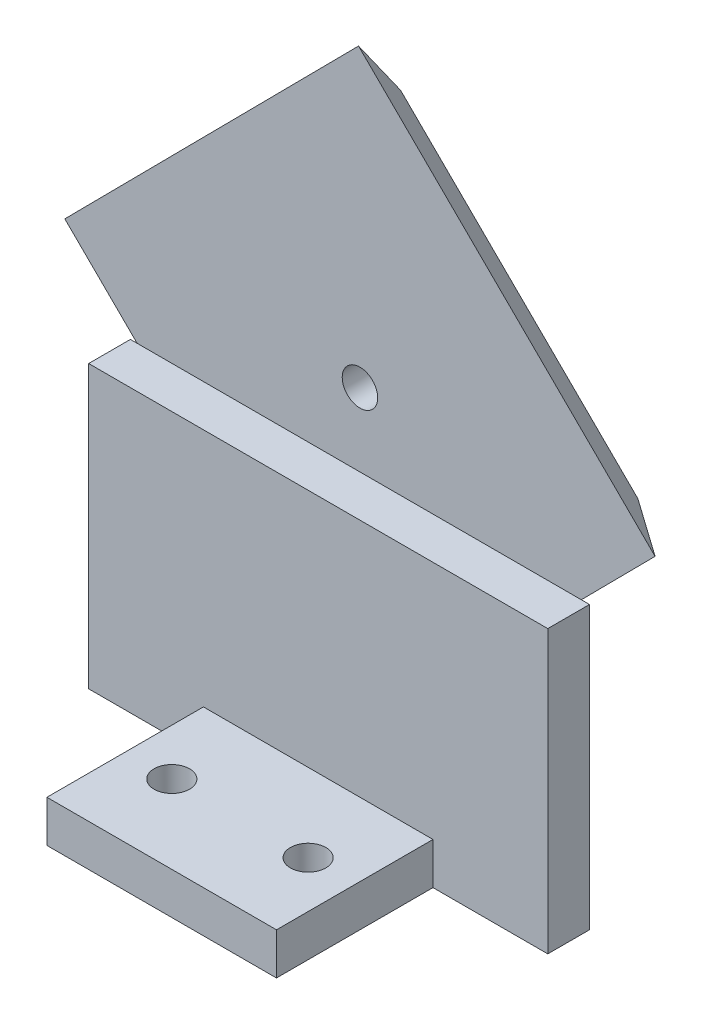
SolidWorks part; units mm, degrees
ref_plane "Спереди" through (0, 0, 0) normal (0, 0, 1) x (1, 0, 0)
ref_plane "Сверху" through (0, 0, 0) normal (0, 1, 0) x (1, 0, 0)
ref_plane "Справа" through (0, 0, 0) normal (1, 0, 0) x (0, 0, -1)
sketch "Эскиз1" plane through (0, 0, 0) normal (0, 1, 0) x (1, 0, 0)
  line L0 (-11, 7.5) -> (-11, 11.5)
  line L1 (11, 7.5) -> (-11, 7.5)
  line L2 (11, 7.5) -> (11, -7.5)
  line L3 (11, -7.5) -> (-11, -7.5)
  line L4 (-11, 7.5) -> (-11, -7.5)
  line L5 (11, 7.5) -> (-11, -7.5) construction
  line L6 (11, -7.5) -> (-11, 7.5) construction
  line L7 (-11, 11.5) -> (11, 11.5)
  line L8 (11, 11.5) -> (11, 7.5)
  line L9 (0, 7.5) -> (0, 11.5) construction
  line L10 (11, 11.5) -> (11, 21.5)
  line L11 (-22, 11.5) -> (22, 11.5)
  line L12 (-22, 11.5) -> (-22, 7.5)
  line L13 (-22, 7.5) -> (22, 7.5)
  line L14 (22, 11.5) -> (22, 7.5)
  line L15 (-22, 11.5) -> (22, 7.5) construction
  line L16 (-22, 7.5) -> (22, 11.5) construction
  line L17 (11, 21.5) -> (-11, 21.5)
  line L18 (-11, 21.5) -> (-11, 11.5)
  point P0 (0, 0)
  point P10 (0, 9.5)
  dimension "D1" = 22
  dimension "D2" = 15
  dimension "D3" = 4
  dimension "D4" = 44
  dimension "D5" = 10
extrude "Бобышка-Вытянуть1" add sketch "Эскиз1" along normal blind 4 contours L1 L4 L3 L2 region at (0, 0, 0)
sketch "Эскиз2" plane through (0, 0, 0) normal (0, -1, 0) x (1, 0, 0)
  line L0 (6.5317, 0) -> (-6.5317, 0)
  point P4 (0, 0)
  point P6 (6.5317, 0)
  point P7 (-6.5317, 0)
hole_wizard "Зенковка для винта с потайной головкой M31" positions "Трехмерный эскиз1" profile "Эскиз3" countersink size "M3" standard "DIN" end condition up to next
sketch3d "Трехмерный эскиз1"
  point P0 (6.5317, 0, 0)
  point P3 (-6.5317, 0, 0)
sketch "Эскиз3" plane through (6.5317, 0, 0) normal (1, 0, 0) x (0, 0, -1)
  line L0 (0, 0) -> (0, 4)
  line L1 (0, 4) -> (1.7, 4)
  line L2 (1.7, 4) -> (1.7, 1.45)
  line L3 (1.7, 1.45) -> (3.15, 0)
  line L5 (3.15, 0) -> (0, 0)
  line L6 (-1.7, 1.45) -> (-3.15, 0) construction
  line L11 (0, -6.35) -> (0, 107.95) construction
  dimension "Диаметр сквозного отверстия" = 3.4
  dimension "Глубина сквозного отверстия" = 4
  dimension "Диаметр передней зенковки" = 6.3
  dimension "Угол передней зенковки" = 90
extrude "Бобышка-Вытянуть2" add sketch "Эскиз1<5>" along normal blind 27 contours L14 L11 L8 L13 | L8 L7 L0 L1 | L12 L13 L0 L11 region at (-16.5, 0, -9.5) region at (0, 0, -9.5) region at (16.5, 0, -9.5)
sketch "Эскиз1<5>" plane through (0, 0, 0) normal (0, 1, 0) x (1, 0, 0) same geometry as "Эскиз1"
sketch "Эскиз4" plane through (0, 0, -11.5) normal (0, 0, -1) x (-1, 0, 0)
  line L0 (0, 0) -> (0, 34) construction
  line L1 (22, 0) -> (-22, 0) construction
  line L2 (0.1363, 62.2839) -> (28.2839, 33.8637)
  line L3 (0.1363, 62.2839) -> (-28.2839, 34.1363)
  line L4 (28.2839, 33.8637) -> (-0.1363, 5.7161)
  line L5 (-28.2839, 34.1363) -> (-0.1363, 5.7161)
  line L6 (0.1363, 62.2839) -> (-0.1363, 5.7161) construction
  line L7 (28.2839, 33.8637) -> (-28.2839, 34.1363) construction
  dimension "D1" = 34
  dimension "D2" = 40
extrude "Бобышка-Вытянуть3" add sketch "Эскиз4" along normal blind 4
draft "Уклон2" type of draft neutral plane draft angle 45 faces to draft 4 face at (15.6113, 21.3409, -13.1) face at (14.0738, 48.2101, -13.5) face at (-14.2101, 48.0738, -13.5) face at (-15.5298, 21.2319, -13.1) neutral plane through (0, 27, -11.5) neutral plane normal (0, 0, -1) parameters "D1"=45
sketch "Эскиз6" plane through (0, 0, -15.5) normal (0, 0, -1) x (-1, 0, 0)
  line L0 (-22.6272, 34.1091) -> (22.6272, 33.8909) construction
  point P4 (0, 34)
hole_wizard "Зенковка для винта с потайной головкой M32" positions "Трехмерный эскиз2" profile "Эскиз7" countersink size "M3" standard "DIN" end condition up to next
sketch3d "Трехмерный эскиз2"
  point P0 (0, 34, -15.5)
sketch "Эскиз7" plane through (0, 34, -15.5) normal (1, 0, 0) x (0, 1, 0)
  line L0 (0, 0) -> (0, 4)
  line L1 (0, 4) -> (1.7, 4)
  line L2 (1.7, 4) -> (1.7, 1.45)
  line L3 (1.7, 1.45) -> (3.15, 0)
  line L5 (3.15, 0) -> (0, 0)
  line L6 (-1.7, 1.45) -> (-3.15, 0) construction
  line L11 (0, -6.35) -> (0, 107.95) construction
  dimension "Диаметр сквозного отверстия" = 3.4
  dimension "Глубина сквозного отверстия" = 4
  dimension "Диаметр передней зенковки" = 6.3
  dimension "Угол передней зенковки" = 90
extrude "Бобышка-Вытянуть4" add sketch "Эскиз1<6>" along normal blind 4 contours L17 L18 L7 L10 region at (0, 0, -16.5)
sketch "Эскиз1<6>" plane through (0, 0, 0) normal (0, 1, 0) x (1, 0, 0) same geometry as "Эскиз1"
